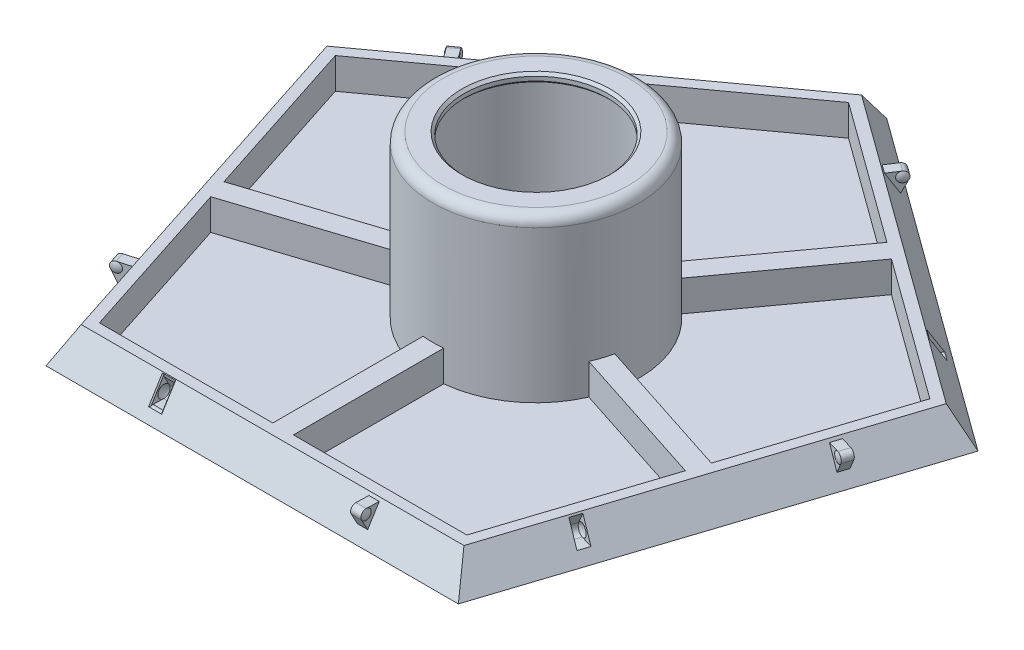
SolidWorks part; units mm, degrees
ref_plane "Front Plane" through (0, 0, 0) normal (0, 0, 1) x (1, 0, 0)
ref_plane "Top Plane" through (0, 0, 0) normal (0, 1, 0) x (1, 0, 0)
ref_plane "Right Plane" through (0, 0, 0) normal (1, 0, 0) x (0, 0, -1)
sketch "Sketch1" plane through (0, 0, 0) normal (0, 1, 0) x (1, 0, 0)
  line L1 (0, 68.0521) -> (-64.7214, 21.0292)
  line L2 (-64.7214, 21.0292) -> (-40, -55.0553)
  line L3 (-40, -55.0553) -> (40, -55.0553)
  line L4 (40, -55.0553) -> (64.7214, 21.0292)
  line L5 (64.7214, 21.0292) -> (0, 68.0521)
  circle A0 centre (0, 0) radius 55.0553 construction
  dimension "D1" = 80
extrude "Boss-Extrude1" add sketch "Sketch1" along normal blind 0.4
sketch "Sketch2" plane through (0, 0.4, 0) normal (0, 1, 0) x (1, 0, 0)
  line L0 (57.6679, 18.7374) -> (0, 60.6357)
  line L1 (0, 60.6357) -> (-57.6679, 18.7374)
  line L2 (-57.6679, 18.7374) -> (-35.6407, -49.0553)
  line L3 (-35.6407, -49.0553) -> (35.6407, -49.0553)
  line L4 (35.6407, -49.0553) -> (57.6679, 18.7374)
  line L5 (64.7214, 21.0292) -> (0, 68.0521)
  line L6 (0, 68.0521) -> (-64.7214, 21.0292)
  line L7 (-64.7214, 21.0292) -> (-40, -55.0553)
  line L8 (-40, -55.0553) -> (40, -55.0553)
  line L9 (40, -55.0553) -> (64.7214, 21.0292)
  line L10 (64.7214, 21.0292) -> (0, 68.0521)
  line L11 (0, 68.0521) -> (-64.7214, 21.0292)
  line L12 (-64.7214, 21.0292) -> (-40, -55.0553)
  line L13 (-40, -55.0553) -> (40, -55.0553)
  line L14 (40, -55.0553) -> (64.7214, 21.0292)
  dimension "D1" = 0
  dimension "D2" = 6
extrude "Boss-Extrude2" add sketch "Sketch2" along normal blind 6
chamfer "Chamfer1" distance 6.4 angle 31.717 5 edges at (-32.3607, 6.4, -44.5407) (32.3607, 6.4, -44.5407) (52.3607, 6.4, 17.013) (0, 6.4, 55.0553) (-52.3607, 6.4, 17.013) first distance on face at (-32.3607, 3.2, -44.5407) first distance on face at (32.3607, 3.2, -44.5407) first distance on face at (52.3607, 3.2, 17.013) first distance on face at (0, 3.2, 55.0553) first distance on face at (-52.3607, 3.2, 17.013)
ref_plane "Plane1" through (20, 0, 0) normal (1, 0, 0) x (0, 0, -1)
sketch "Sketch3" plane through (20, 0, 0) normal (1, 0, 0) x (0, 0, -1)
  line L0 (-51.0999, 0) -> (-55.0553, 0) construction
  line L1 (-55.0553, 0) -> (21.0292, 0) construction
  line L2 (-55.0553, 0) -> (-51.0999, 6.4) construction
  line L3 (-55.0553, 0) -> (-56.8242, 3.5378) construction
  line L5 (-51.0999, 6.4) -> (-56.8242, 3.5378) construction
  line L6 (-51.0999, 6.4) -> (-51.0999, 0) construction
  line L7 (-51.0999, 3.2) -> (-53.0776, 3.2) construction
  line L8 (-53.0776, 3.2) -> (-53.962, 4.9689) construction
  line L9 (-54.8426, 4.4951) -> (-53.6486, 2.276)
  line L12 (-51.4132, 5.8929) -> (-53.9321, 5.9685)
  line L13 (-53.962, 4.9689) -> (-51.0999, 3.2) construction
  line L16 (-51.4132, 5.8929) -> (-53.6486, 2.276)
  line L17 (-51.1298, 2.2004) -> (-53.6486, 2.276) construction
  line L18 (-51.4132, 5.8929) -> (-50.2192, 3.6738) construction
  arc A0 (-53.9321, 5.9685) -> (-54.8426, 4.4951) centre (-53.962, 4.9689) ccw
  arc A1 (-50.2192, 3.6738) -> (-51.1298, 2.2004) centre (-51.0999, 3.2) cw construction
  dimension "D2" = 2
  dimension "D1" = 30
extrude "Boss-Extrude3" add sketch "Sketch3" along normal mid plane 2
ref_axis "Axis1" through (21, 4.9689, 53.962) along (-1, 0, 0)
ref_plane "Plane2" through (0, 4.9689, 0) normal (0, 1, 0) x (-1, 0, 0)
sketch "Sketch5" plane through (0, 4.9689, 0) normal (0, 1, 0) x (-1, 0, 0)
  line L0 (-21, 53.962) -> (-19, 53.962) construction
  line L1 (-21, 54.962) -> (-21, 53.962)
  line L2 (-21, 54.962) -> (-21, 53.9321) construction
  line L4 (-21, 53.962) -> (-21.25, 53.962)
  arc A0 (-21, 54.962) -> (-21.25, 53.962) centre (-19.125, 53.962) ccw
  dimension "D2" = 0.25
revolve "Revolve1" add sketch "Sketch5" angle 360 about L4
mirror "Mirror1" about plane through (20, 0, 0) normal (1, 0, 0) of "Revolve1"
ref_plane "Plane3" through (-20, 0, 0) normal (1, 0, 0) x (0, 0, -1)
sketch "Sketch6" plane through (-20, 0, 0) normal (1, 0, 0) x (0, 0, -1)
  line L0 (-51.4132, 5.8929) -> (-53.6486, 2.276) construction
  line L1 (-51.1298, 2.2004) -> (-53.6486, 2.276) construction
  line L2 (-51.4132, 5.8929) -> (-50.2192, 3.6738) construction
  line L3 (-51.4132, 5.8929) -> (-53.6486, 2.276) construction
  line L4 (-51.1298, 2.2004) -> (-53.6486, 2.276) construction
  line L5 (-51.4132, 5.8929) -> (-50.2192, 3.6738) construction
  line L6 (-51.4013, 6.2928) -> (-50.0431, 3.7686)
  line L7 (-51.1358, 2.0005) -> (-54.0009, 2.0864)
  line L8 (-51.4013, 6.2928) -> (-54.0009, 2.0864)
  arc A0 (-51.1298, 2.2004) -> (-50.2192, 3.6738) centre (-51.0999, 3.2) ccw construction
  arc A1 (-51.1298, 2.2004) -> (-50.2192, 3.6738) centre (-51.0999, 3.2) ccw construction
  arc A2 (-51.1358, 2.0005) -> (-50.0431, 3.7686) centre (-51.0999, 3.2) ccw
  dimension "D1" = 0.2
extrude "Cut-Extrude1" cut sketch "Sketch6" against normal mid plane 2.15
ref_axis "Axis2" through (-21.075, 3.2, 51.0999) along (1, 0, 0)
ref_plane "Plane4" through (0, 3.2, 0) normal (0, 1, 0) x (1, 0, 0)
sketch "Sketch8" plane through (0, 3.2, 0) normal (0, 1, 0) x (1, 0, 0)
  line L0 (-21.075, -51.0999) -> (-18.925, -51.0999) construction
  line L1 (-21.075, -53.0776) -> (-21.075, -49.8999)
  line L2 (-21.075, -53.0776) -> (-21.075, -49.8999) construction
  line L3 (-21.075, -51.0999) -> (-21.475, -51.0999)
  line L6 (-21.075, -51.0999) -> (-21.075, -49.8999)
  arc A0 (-21.075, -49.8999) -> (-21.475, -51.0999) centre (-19.475, -51.0999) ccw
  dimension "D1" = 0.4
revolve "Cut-Revolve1" cut sketch "Sketch8" angle 360 about L3
mirror "Mirror2" about plane through (-20, 0, 0) normal (1, 0, 0) of "Cut-Revolve1"
ref_axis "Axis3" through (0, 6.72, 0) along (0, -1, 0)
pattern_circular "CirPattern1" count 5 over 360 about axis through (0, 6.72, 0) along (0, -1, 0) of "Boss-Extrude3", "Revolve1", "Mirror1", "Cut-Extrude1", "Cut-Revolve1", "Mirror2"
chamfer "Chamfer2" distance 0.2 angle 45 4 edges at (-20, 2.0795, 53.7701) (-18.925, 4.0845, 52.5309) (-21.075, 4.0845, 52.5309) (-20, 6.0894, 51.2918) first distance on face at (20, 4.0845, 52.5309)
sketch "Sketch9" plane through (0, 0.4, 0) normal (0, 1, 0) x (1, 0, 0)
  circle A0 centre (0, 0) radius 20
  dimension "D1" = 40
extrude "Cut-Extrude2" cut sketch "Sketch9" against normal up to next
sketch "Sketch13" plane through (0, 0, 0) normal (1, 0, 0) x (0, 0, -1)
  line L0 (-16.5, 0) -> (-16.5, 30)
  line L1 (-16.5, 30) -> (-13.9, 30)
  line L2 (-13.9, 30) -> (-13.9, 31.8)
  line L3 (-13.9, 31.8) -> (-20, 31.8)
  line L4 (-20, 31.8) -> (-20, 0)
  line L5 (-20, 0) -> (-16.5, 0)
  line L8 (0, 0) -> (0, 31.8) construction
  line L9 (0, 6.72) -> (0, -0.32) construction
  dimension "D1" = 20
  dimension "D2" = 13.9
  dimension "D3" = 1.8
  dimension "D4" = 16.5
  dimension "D5" = 30
revolve "Revolve2" add sketch "Sketch13" angle 360 about L8
fillet "Fillet1" radius 2 1 edges at (0, 31.8, -20)
chamfer "Chamfer3" distance 0.5 angle 45 2 edges at (0, 30, -13.9) (0, 31.8, -13.9)
sketch "Sketch11" [suppressed] plane through (0, 0.4, 0) normal (0, 1, 0) x (1, 0, 0)
  line L10 (24.7426, -34.0553) -> (40.0344, 13.008)
  line L11 (40.0344, 13.008) -> (0, 42.0946)
  line L12 (0, 42.0946) -> (-40.0344, 13.008)
  line L13 (-40.0344, 13.008) -> (-24.7426, -34.0553)
  line L14 (-24.7426, -34.0553) -> (24.7426, -34.0553)
  line L15 (24.7426, -34.0553) -> (40.0344, 13.008)
  line L16 (40.0344, 13.008) -> (0, 42.0946)
  line L17 (0, 42.0946) -> (-40.0344, 13.008)
  line L18 (-40.0344, 13.008) -> (-24.7426, -34.0553)
  line L19 (-24.7426, -34.0553) -> (24.7426, -34.0553)
  dimension "D1" = 15
extrude "Cut-Extrude3" [suppressed] cut sketch "Sketch11" against normal up to next
sketch "Sketch12" [suppressed] plane through (0, 0.4, 0) normal (0, 1, 0) x (1, 0, 0)
  line L5 (-24.7426, -34.0553) -> (24.7426, -34.0553) construction
  line L6 (24.7426, -34.0553) -> (40.0344, 13.008) construction
  line L7 (40.0344, 13.008) -> (0, 42.0946) construction
  line L8 (-40.0344, 13.008) -> (-24.7426, -34.0553) construction
  line L9 (0, 42.0946) -> (-40.0344, 13.008) construction
  line L10 (-29.1019, -40.0553) -> (29.1019, -40.0553)
  line L11 (29.1019, -40.0553) -> (47.0878, 15.2998)
  line L12 (47.0878, 15.2998) -> (0, 49.511)
  line L13 (-47.0878, 15.2998) -> (-29.1019, -40.0553)
  line L14 (0, 49.511) -> (-47.0878, 15.2998)
  line L15 (-29.1019, -40.0553) -> (29.1019, -40.0553)
  line L16 (29.1019, -40.0553) -> (47.0878, 15.2998)
  line L17 (47.0878, 15.2998) -> (0, 49.511)
  line L18 (-47.0878, 15.2998) -> (-29.1019, -40.0553)
  line L19 (0, 49.511) -> (-47.0878, 15.2998)
  line L20 (-24.7426, -34.0553) -> (24.7426, -34.0553)
  line L21 (24.7426, -34.0553) -> (40.0344, 13.008)
  line L22 (40.0344, 13.008) -> (0, 42.0946)
  line L23 (-40.0344, 13.008) -> (-24.7426, -34.0553)
  line L24 (0, 42.0946) -> (-40.0344, 13.008)
  dimension "D1" = 6
extrude "Boss-Extrude5" [suppressed] add sketch "Sketch12" along normal blind 2
sketch "Sketch14" plane through (0, 0.4, 0) normal (0, 1, 0) x (1, 0, 0)
  line L0 (-11.7557, 16.1803) -> (-28.834, 39.6866) construction
  line L1 (0, 60.6357) -> (-57.6679, 18.7374) construction
  line L2 (-10.0787, 17.2748) -> (-27.2159, 40.8621)
  line L3 (-13.3148, 14.9237) -> (-30.452, 38.511)
  line L4 (-13.3737, 15.0048) -> (-30.452, 38.511) construction
  line L5 (-10.1377, 17.3559) -> (-27.2159, 40.8621) construction
  line L6 (-27.2159, 40.8621) -> (-30.452, 38.511)
  circle A1 centre (0, 0) radius 20 construction
  arc A2 (-10.0787, 17.2748) -> (-13.3148, 14.9237) centre (0, 0) ccw
  dimension "D1" = 2
  dimension "D2" = 2
extrude "Boss-Extrude6" add sketch "Sketch14" along normal up to surface (6 mm away) up to face at (0, 6.4, 0)
pattern_circular "CirPattern4" count 5 over 360 about axis through (0, 0, 0) along (0, -1, 0) of "Boss-Extrude6"
